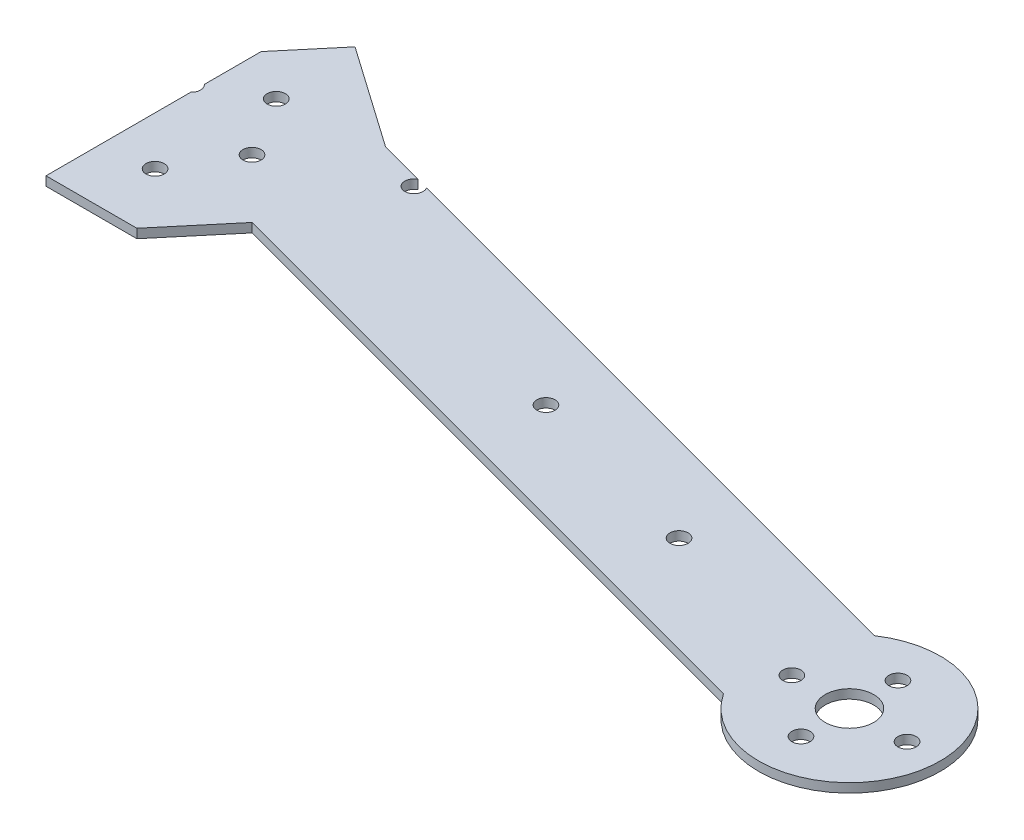
SolidWorks part; units mm, degrees
other "Markup1"
sketch "Sketch5" plane through (0, 1.5, 8.4265) normal (-0.2691, 0.6708, 0.6911) x (0.9345, 0.0084, 0.3557)
ref_plane "Front Plane" through (0, 0, 0) normal (0, 0, 1) x (1, 0, 0)
ref_plane "Top Plane" through (0, 0, 0) normal (0, 1, 0) x (1, 0, 0)
ref_plane "Right Plane" through (0, 0, 0) normal (1, 0, 0) x (0, 0, -1)
sketch "Sketch2" plane through (0, 0, 0) normal (0, 1, 0) x (1, 0, 0)
  line L25 (7.0707, -17.6306) -> (28.2625, -17.6306) construction
  line L26 (142.4295, -80.5981) -> (142.4295, -86.6558) construction
  line L27 (147.7774, -80.5981) -> (142.4295, -80.5981) construction
  line L28 (136.0028, -80.5981) -> (147.7774, -80.5981) construction
  line L29 (23.6776, -60.4195) -> (23.8633, -38.593) construction
  line L30 (0, -46.8792) -> (0, -70.7611)
  line L31 (142.4295, -80.5981) -> (142.4295, -75.2609)
  line L32 (23.8633, -38.593) -> (134.0979, -68.1247)
  line L33 (7.0707, -26.8346) -> (23.8633, -38.593)
  line L34 (0, -35.2611) -> (7.0707, -26.8346)
  line L35 (23.6776, -60.4195) -> (129.9295, -88.8896)
  line L36 (15, -70.7611) -> (23.6776, -60.4195)
  line L37 (0, -70.7611) -> (15, -70.7611)
  line L38 (0, -35.2611) -> (0, -44.6431)
  arc A14 (0, -44.6431) -> (0, -46.8792) centre (-1, -45.7611) cw
  circle A15 centre (8, -40.7611) radius 1.5
  circle A16 centre (14, -50.7611) radius 1.5
  circle A17 centre (8, -60.7611) radius 1.5
  circle A18 centre (142.4295, -80.5981) radius 4
  arc A19 (134.0979, -68.1247) -> (129.9295, -88.8896) centre (142.4295, -80.5981) cw
  circle A28 centre (142.4295, -72.5981) radius 1.5
  circle A29 centre (151.9295, -80.5981) radius 1.5
  circle A30 centre (142.4295, -88.5981) radius 1.5
  circle A31 centre (132.9295, -80.5981) radius 1.5
  point P8 (142.4295, -80.9867)
  point P9 (0, 0)
  point P95 (142.4295, -80.5981)
  dimension "D1" = 16
  dimension "D2" = 8
  dimension "D3" = 19
  dimension "D4" = 9.5
extrude "Boss-Extrude1" add sketch "Sketch2" along normal blind 1.5 contours A14 L30 L37 L36 L35 A19 L32 L33 L34 L38 | A15 | A16 | A17 | A18 | A31 | A30 | A29 | A28
sketch "Sketch6" plane through (0, 1.5, 0) normal (0, 1, 0) x (1, 0, 0)
  circle A0 centre (31.86, -41.9011) radius 1.5
  circle A1 centre (14, -50.7611) radius 1.5 construction
  dimension "D1" = 3
  dimension "D2" = 17.86
  dimension "D3" = 8.86
extrude "Cut-Extrude1" cut sketch "Sketch6" against normal up to surface (1.5 mm away) up to face at (151.9295, 0, 82.0981)
sketch "Sketch7" plane through (0, 1.5, 0) normal (0, 1, 0) x (1, 0, 0)
  line L0 (23.8633, -38.593) -> (134.0979, -68.1247) construction
  line L1 (142.4295, -80.5981) -> (23.994, -48.8693) construction
  circle A0 centre (74.0141, -62.2696) radius 1.5
  circle A1 centre (104.0141, -70.3066) radius 1.5
  dimension "D1" = 3
  dimension "D2" = 3
  dimension "D3" = 30
  dimension "D4" = 39.77
extrude "Cut-Extrude2" cut sketch "Sketch7" against normal up to surface (1.5 mm away) up to face at (35.2404, 0, 53.3645)
